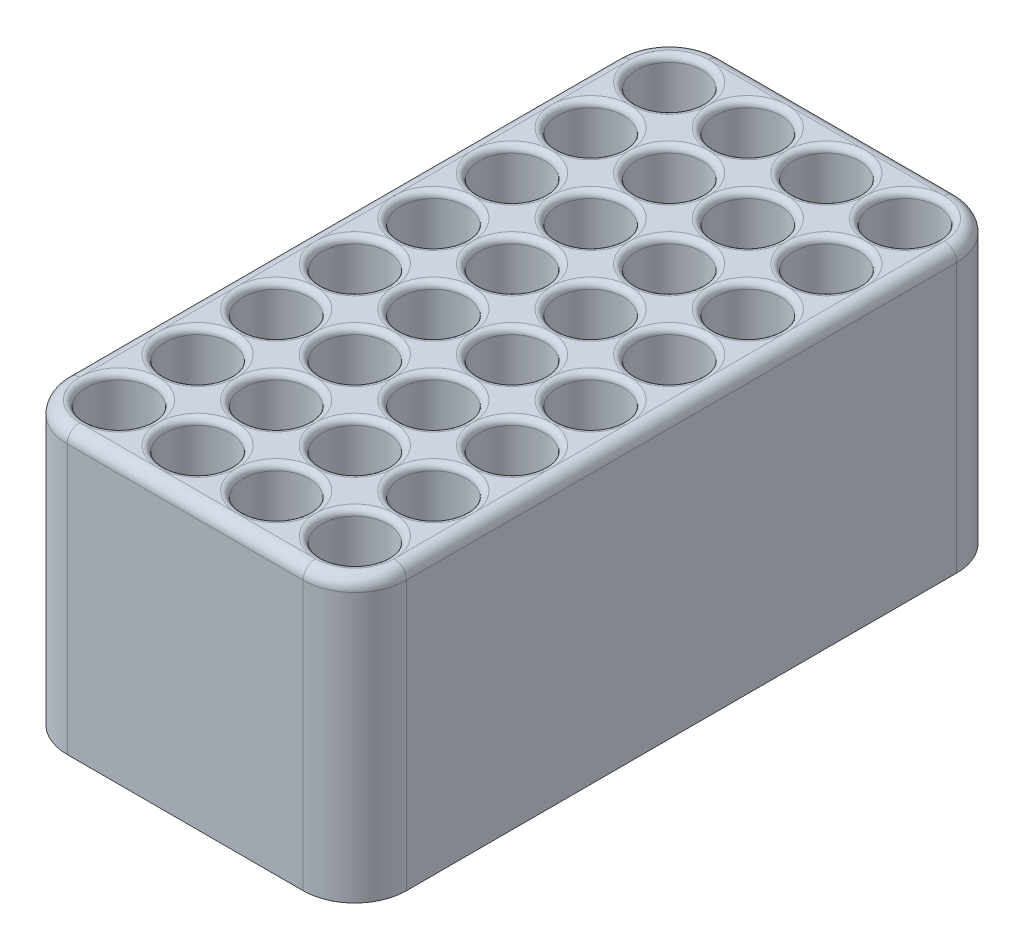
SolidWorks part; units mm, degrees
ref_plane "Front Plane" through (0, 0, 0) normal (0, 0, 1) x (1, 0, 0)
ref_plane "Top Plane" through (0, 0, 0) normal (0, 1, 0) x (1, 0, 0)
ref_plane "Right Plane" through (0, 0, 0) normal (1, 0, 0) x (0, 0, -1)
sketch "Sketch1" plane through (0, 0, 0) normal (0, 1, 0) x (1, 0, 0)
  line L1 (-7.5406, -7.5406) -> (7.5406, -7.5406)
  line L2 (-7.5406, -7.5406) -> (-7.5406, 7.5406)
  line L3 (-7.5406, 7.5406) -> (7.5406, 7.5406)
  line L4 (7.5406, -7.5406) -> (7.5406, 7.5406)
  line L5 (-7.5406, -7.5406) -> (7.5406, 7.5406) construction
  line L6 (-7.5406, 7.5406) -> (7.5406, -7.5406) construction
  circle A0 centre (0, 0) radius 6.35
  dimension "D1" = 12.7
  dimension "D2" = 15.0812
extrude "Boss-Extrude1" add sketch "Sketch1" along normal blind 50.8
sketch "Sketch4" plane through (0, 0, 0) normal (0, -1, 0) x (1, 0, 0)
  line L4 (7.5406, -7.5406) -> (7.5406, 7.5406)
  line L5 (7.5406, 7.5406) -> (-7.5406, 7.5406)
  line L6 (-7.5406, 7.5406) -> (-7.5406, -7.5406)
  line L7 (-7.5406, -7.5406) -> (7.5406, -7.5406)
  line L8 (7.5406, -7.5406) -> (7.5406, 7.5406)
  line L9 (7.5406, 7.5406) -> (-7.5406, 7.5406)
  line L10 (-7.5406, 7.5406) -> (-7.5406, -7.5406)
  line L11 (-7.5406, -7.5406) -> (7.5406, -7.5406)
  dimension "D1" = 0
extrude "Boss-Extrude4" add sketch "Sketch4" along normal blind 3.175
fillet "Fillet3" radius 1.1906 2 edges at (0, 0, 6.35) (0, 50.8, 6.35)
pattern_linear "LPattern2" count 4 spacing 15.0812 along (1, 0, 0) count 8 spacing 15.0812 along (0, 0, 1) of "Boss-Extrude1", "Boss-Extrude4", "Fillet3"
sketch "Sketch5" plane through (0, -3.175, 0) normal (0, -1, 0) x (1, 0, 0)
  line L4 (52.7844, 113.1094) -> (-7.5406, 113.1094)
  line L5 (-7.5406, 113.1094) -> (-7.5406, -7.5406)
  line L6 (-7.5406, -7.5406) -> (52.7844, -7.5406)
  line L9 (-7.5406, 113.1094) -> (-7.5406, -7.5406)
  line L10 (-7.5406, -7.5406) -> (52.7844, -7.5406)
  line L16 (55.1656, 115.4906) -> (-9.9219, 115.4906)
  line L17 (-9.9219, 115.4906) -> (-9.9219, -9.9219)
  line L18 (-9.9219, -9.9219) -> (55.1656, -9.9219)
  line L21 (-9.9219, 115.4906) -> (-9.9219, -9.9219)
  line L22 (-9.9219, -9.9219) -> (55.1656, -9.9219)
  line L30 (52.7844, -7.5406) -> (52.7844, 113.1094)
  line L31 (52.7844, -7.5406) -> (52.7844, 113.1094)
  line L32 (55.1656, -9.9219) -> (55.1656, 115.4906)
  line L33 (55.1656, -9.9219) -> (55.1656, 115.4906)
  line L36 (52.7844, 113.1094) -> (-7.5406, 113.1094)
  line L37 (55.1656, 115.4906) -> (-9.9219, 115.4906)
  dimension "D2" = 2.3813
extrude "Boss-Extrude5" add sketch "Sketch5" against normal up to surface (53.975 mm away) up to face at (37.7031, 50.8, 98.0281)
fillet "Fillet4" radius 9.9219 4 edges at (55.1656, 23.8125, -9.9219) (-9.9219, 23.8125, -9.9219) (-9.9219, 23.8125, 115.4906) (55.1656, 23.8125, 115.4906)
fillet "Fillet5" radius 2.3813 8 edges at (-7.0158, 50.8, -7.0158) (22.6219, 50.8, -9.9219) (52.2596, 50.8, -7.0158) (55.1656, 50.8, 52.7844) (-9.9219, 50.8, 52.7844) (52.2596, 50.8, 112.5846) (22.6219, 50.8, 115.4906) (-7.0158, 50.8, 112.5846)
hole_wizard "CSK for #10 Flat Head Machine Screw (100)1" positions "Sketch8" profile "Sketch7" countersink size "#10" standard "ANSI Inch" end condition through all
sketch "Sketch8" plane through (0, 0, 0) normal (0, 1, 0) x (1, 0, 0)
  point P0 (45.2437, 0)
  point P3 (0, -30.1625)
  point P9 (0, -105.5687)
  point P13 (45.2437, -75.4062)
sketch "Sketch7" plane through (45.2437, 0, 0) normal (1, 0, 0) x (0, 0, 1)
  line L0 (0, 0) -> (0, 3.175)
  line L1 (0, 3.175) -> (2.5527, 3.175)
  line L2 (2.5527, 3.175) -> (2.5527, 1.9608)
  line L3 (2.5527, 1.9608) -> (4.8895, 0)
  line L5 (4.8895, 0) -> (0, 0)
  line L6 (-2.5527, 1.9608) -> (-4.8895, 0) construction
  line L11 (0, -6.35) -> (0, 107.95) construction
  dimension "Thru Hole Dia." = 5.1054
  dimension "Thru Hole Depth" = 3.175
  dimension "Near C'Sink Dia." = 9.779
  dimension "Near C'Sink Angle" = 100
equation "\"width\"= 4"
equation "\"D1@LPattern2\"=\"width\""
equation "\"length\" = 8"
equation "\"D2@LPattern2\"=\"length\""
equation "\"hold_diameter\"= .5"
equation "\"width_between_hole\"= 3 / 32"
equation "\"D2@Sketch1\"=\"hold_diameter\"+\"width_between_hole\""
equation "\"D1@Sketch1\"=\"hold_diameter\""
equation "\"D4@LPattern2\"=\"width_between_hole\"+\"hold_diameter\""
equation "\"D3@LPattern2\"=\"hold_diameter\"+\"width_between_hole\""
equation "\"D1@Fillet3\"=\"width_between_hole\"/2"
equation "\"outer_lip_thickness\" = 3 / 32"
equation "\"D2@Sketch5\"=\"outer_lip_thickness\""
equation "\"D1@Fillet5\"=\"outer_lip_thickness\""
equation "\"height\"= 2"
equation "\"D1@Boss-Extrude1\"=\"height\""
equation "\"bottom_thickness\" = 0.125"
equation "\"D1@Boss-Extrude4\"=\"bottom_thickness\""
equation "\"D1@Fillet4\"=(\"hold_diameter\"+\"width_between_hole\")/2+\"outer_lip_thickness\""
